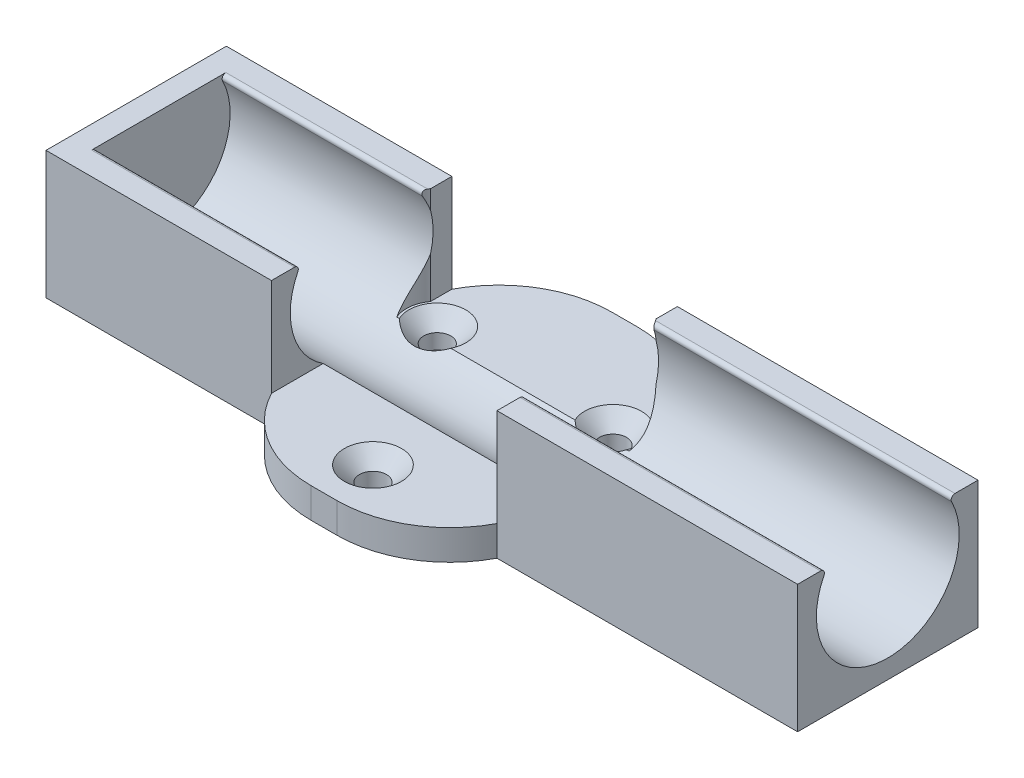
SolidWorks part; units mm, degrees
ref_plane "Спереди" through (0, 0, 0) normal (0, 0, 1) x (1, 0, 0)
ref_plane "Сверху" through (0, 0, 0) normal (0, 1, 0) x (1, 0, 0)
ref_plane "Справа" through (0, 0, 0) normal (1, 0, 0) x (0, 0, -1)
sketch "Эскиз6" plane through (0, 0, 0) normal (0, 1, 0) x (1, 0, 0)
  line L0 (0, 20) -> (0, 12)
  line L1 (0, 20) -> (30, 20)
  line L2 (30, 20) -> (30, 12)
  line L3 (30, 12) -> (70, 12)
  line L4 (70, 12) -> (70, -12)
  line L5 (0, 56.0118) -> (0, 0) construction
  line L6 (0, 0) -> (129.6915, 0) construction
  line L7 (0, 12) -> (-30, 12)
  line L8 (-30, 12) -> (-30, -12)
  line L9 (0, -20) -> (0, -12)
  line L10 (0, -12) -> (-30, -12)
  line L11 (30, -12) -> (70, -12)
  line L12 (30, -20) -> (30, -12)
  line L13 (0, -20) -> (30, -20)
  point P15 (-30, 0)
  point P16 (70, 0)
  dimension "D1" = 24
  dimension "D2" = 30
  dimension "D3" = 8
  dimension "D4" = 30
  dimension "D5" = 40
extrude "Бобышка-Вытянуть2" add sketch "Эскиз6" along normal blind 4
sketch "Эскиз7" plane through (0, 4, 0) normal (0, 1, 0) x (1, 0, 0)
  line L1 (-30, 12) -> (70, 12)
  line L2 (-30, 12) -> (-30, -12)
  line L3 (-30, -12) -> (70, -12)
  line L4 (70, 12) -> (70, -12)
extrude "Бобышка-Вытянуть3" add sketch "Эскиз7" along normal blind 13
sketch "Эскиз8" plane through (70, 0, 0) normal (1, 0, 0) x (0, 0, -1)
  line L0 (-12, 17) -> (12, 17) construction
  circle A0 centre (0, 12) radius 9.5
  dimension "D1" = 19
  dimension "D2" = 5
extrude "Вырез-Вытянуть3" cut sketch "Эскиз8" against normal offset from surface (97 mm away) 3 up to face at (-30, 8.5, 0)
sketch "Эскиз9" plane through (0, 0, 12) normal (0, 0, 1) x (1, 0, 0)
  line L0 (-30, 17) -> (70, 17) construction
  line L1 (0, 17) -> (30, 17)
  line L2 (0, 17) -> (0, 4)
  line L3 (0, 4) -> (30, 4)
  line L4 (30, 17) -> (30, 4)
  line L5 (-30, 17) -> (-30, 0) construction
  dimension "D1" = 30
  dimension "D2" = 30
extrude "Вырез-Вытянуть4" cut sketch "Эскиз9" against normal through all
sketch "Эскиз10" plane through (0, 4, 0) normal (0, 1, 0) x (1, 0, 0)
  line L0 (0, 0) -> (111.8319, 0) construction
  circle A0 centre (15, 0) radius 13.5 construction
  circle A1 centre (15, -13.5) radius 1.8
  circle A2 centre (3.3087, 6.75) radius 1.8
  circle A3 centre (26.6913, 6.75) radius 1.8
  point P7 (15, 0)
  point P14 (15, 0)
  dimension "D1" = 27
  dimension "D2" = 3.6
  dimension "D4" = 15
  dimension "D3" = 3
extrude "Вырез-Вытянуть5" cut sketch "Эскиз10" against normal through all
fillet "Скругление3" radius 15 4 edges at (30, 2, -20) (0, 2, -20) (30, 2, 20) (0, 2, 20)
fillet "Скругление4" radius 0.5 4 edges at (-13.5, 17, 8.0777) (-13.5, 17, -8.0777) (50, 17, -8.0777) (50, 17, 8.0777)
sketch "Эскиз11" plane through (0, 17, 0) normal (0, 1, 0) x (1, 0, 0)
  circle A0 centre (15, 0) radius 13.5 construction
  circle A1 centre (15, -13.5) radius 4.1
  circle A2 centre (3.3087, 6.75) radius 4.1
  circle A3 centre (26.6913, 6.75) radius 4.1
  point P10 (15, 0)
  dimension "D1" = 27
  dimension "D2" = 3
  dimension "D3" = 8.2
extrude "Вырез-Вытянуть9" cut sketch "Эскиз11" against normal up to surface (13 mm away) up to face at (15, 4, 15.3)
chamfer "Фаска2" distance 2 angle 45 1 edges at (26.6913, 4, -8.55)
chamfer "Фаска1" distance 2 angle 45 2 edges at (15, 4, 15.3) (3.3087, 4, -8.55)
